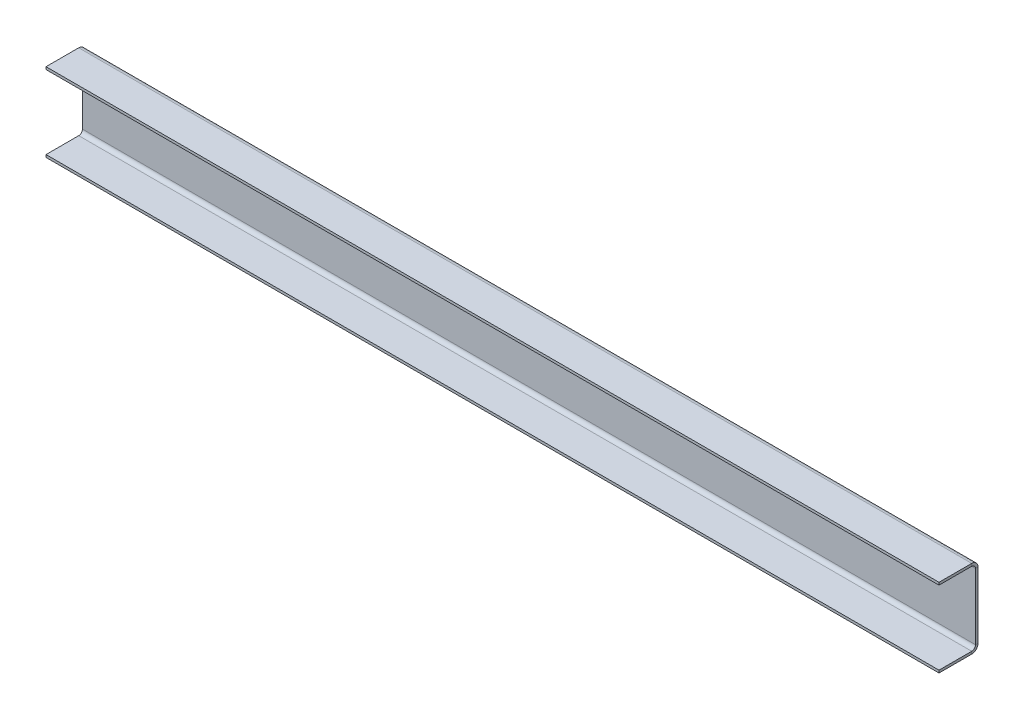
SolidWorks part; units mm, degrees
note: The reader was unsure of these and kept them because the rebuilt part matched: flange length of "Edge-Flange1", "Edge-Flange2".
material "ASTM A36 Steel"
ref_plane "Front Plane" through (0, 0, 0) normal (0, 0, 1) x (1, 0, 0)
ref_plane "Top Plane" through (0, 0, 0) normal (0, 1, 0) x (1, 0, 0)
ref_plane "Right Plane" through (0, 0, 0) normal (1, 0, 0) x (0, 0, -1)
sketch "Sketch1" plane through (0, 0, 0) normal (0, 0, 1) x (1, 0, 0)
  line L1 (483.1277, 106.8867) -> (-936.8723, 106.8867)
  line L2 (483.1277, 106.8867) -> (483.1277, -18.1133)
  line L3 (483.1277, -18.1133) -> (-936.8723, -18.1133)
  line L4 (-936.8723, 106.8867) -> (-936.8723, -18.1133)
  dimension "D1" = 1420
  dimension "D2" = 125
base flange "Base-Flange1" sketch "Sketch1" thickness 4 reverse thickness direction no parameters "D1"=2.5
edge flange "Edge-Flange1" sketch "Sketch8" flange angle 90 flange length 62 flange position material inside bend radius 6 thickness 4 relief rectangular parameters "D6"=10
sketch "Sketch8" plane through (0, 106.8867, 0) normal (0, -1, 0) x (1, 0, 0)
  line L1 (483.1277, 0) -> (-936.8723, 0) construction
  line L2 (-936.8723, 0) -> (-936.8723, 58)
  line L3 (-936.8723, 58) -> (483.1277, 58)
  line L4 (483.1277, 58) -> (483.1277, 0)
  line L5 (483.1277, 0) -> (-936.8723, 0)
bend "EdgeBend1" bend radius 6 bend angle 90 parameters "D5"=1
edge flange "Edge-Flange2" sketch "Sketch11" flange angle 90 flange length 62 flange position material inside bend radius 6 thickness 4 relief rectangular parameters "D6"=10
sketch "Sketch11" plane through (0, -18.1133, 0) normal (0, 1, 0) x (-1, 0, 0)
  line L1 (936.8723, 0) -> (-483.1277, 0) construction
  line L2 (-483.1277, 0) -> (-483.1277, 58)
  line L3 (-483.1277, 58) -> (936.8723, 58)
  line L4 (936.8723, 58) -> (936.8723, 0)
  line L5 (936.8723, 0) -> (-483.1277, 0)
bend "EdgeBend2" bend radius 6 bend angle 90 parameters "D5"=2
sketch "Bend-Lines1" [suppressed] plane through (0, 0, 0) normal (0, 1, 0) x (1, 0, 0)
sketch "Bounding-Box1" [suppressed] plane through (0, 0, 0) normal (0, 1, 0) x (1, 0, 0)
sheet metal parameters "Sheet-Metal1" thickness 4 parameters "D1"=2.5
flat pattern "Flat-Pattern1" [suppressed]
sketch "Bend-Lines2" plane through (0, 0, 0) normal (0, 1, 0) x (1, 0, 0)
sketch3d "Bounding-Box2" [suppressed]
  line L0 (708.8723, -18.1133, 0) -> (-483.1277, -18.1133, 0) construction
  line L1 (708.8723, 106.8867, 0) -> (-483.1277, 106.8867, 0) construction
  line L2 (708.8723, -18.1133, 0) -> (708.8723, 106.8867, 0) construction
  line L3 (-483.1277, -18.1133, 0) -> (-483.1277, 106.8867, 0) construction
sheet metal parameters "Sheet-Metal2" thickness 4 parameters "D1"=2.5
flat pattern "Flat-Pattern1"
sketch "Bend-Lines2" plane through (0, 0, 0) normal (0, 0, 1) x (1, 0, 0)
  line L0 (483.1277, 103.1698) -> (-708.8723, 103.1698) construction
  line L1 (483.1277, 103.1698) -> (-708.8723, 103.1698) construction
sketch3d "Bounding-Box2" [suppressed]
  line L0 (-708.8723, -18.1133, 0) -> (483.1277, -18.1133, 0) construction
  line L1 (-708.8723, 161.453, 0) -> (483.1277, 161.453, 0) construction
  line L2 (-708.8723, -18.1133, 0) -> (-708.8723, 161.453, 0) construction
  line L3 (483.1277, -18.1133, 0) -> (483.1277, 161.453, 0) construction
bend of the flat pattern "Flatten-<EdgeBend1>1"
sheet metal parameters "Sheet-Metal3" thickness 4 parameters "D1"=2.5
flat pattern "Flat-Pattern1"
sketch "Bend-Lines2" plane through (0, 0, 0) normal (0, 0, 1) x (1, 0, 0)
  line L0 (483.1277, 103.1698) -> (-936.8723, 103.1698) construction
  line L1 (483.1277, 103.1698) -> (-936.8723, 103.1698) construction
  line L2 (-936.8723, -14.3965) -> (483.1277, -14.3965) construction
  line L3 (-936.8723, -14.3965) -> (483.1277, -14.3965) construction
sketch3d "Bounding-Box2" [suppressed]
  line L0 (-936.8723, -72.6797, 0) -> (483.1277, -72.6797, 0) construction
  line L1 (-936.8723, 161.453, 0) -> (483.1277, 161.453, 0) construction
  line L2 (-936.8723, -72.6797, 0) -> (-936.8723, 161.453, 0) construction
  line L3 (483.1277, -72.6797, 0) -> (483.1277, 161.453, 0) construction
bend of the flat pattern "Flatten-<EdgeBend1>1"
bend of the flat pattern "Flatten-<EdgeBend2>1"
